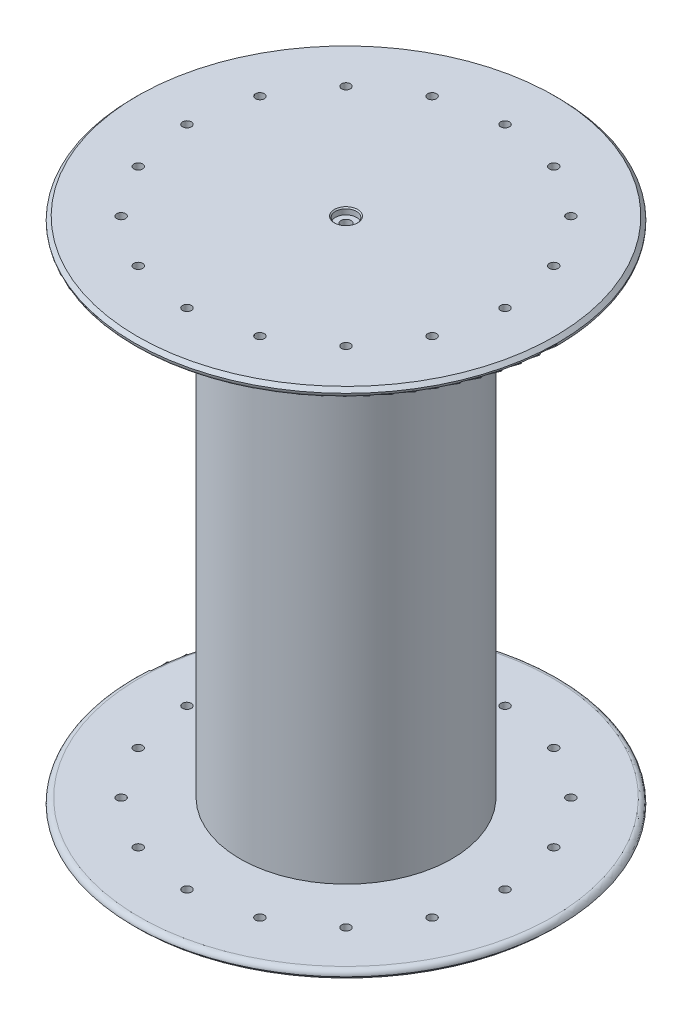
SolidWorks part; units mm, degrees
ref_plane "Front Plane" through (0, 0, 0) normal (0, 0, 1) x (1, 0, 0)
ref_plane "Top Plane" through (0, 0, 0) normal (0, 1, 0) x (1, 0, 0)
ref_plane "Right Plane" through (0, 0, 0) normal (1, 0, 0) x (0, 0, -1)
sketch "Sketch1" plane through (0, 0, 0) normal (0, 1, 0) x (1, 0, 0)
  circle A0 centre (0, 0) radius 60
  dimension "shaftdiameter" = 120
extrude "Boss-Extrude1" add sketch "Sketch1" along normal mid plane 280
ref_plane "Plane1" through (0, 50, 0) normal (0, 1, 0) x (1, 0, 0)
sketch "Sketch3" plane through (0, 140, 0) normal (0, 1, 0) x (1, 0, 0)
  circle A0 centre (0, 0) radius 120
  dimension "capdiameter" = 240
extrude "Boss-Extrude2" add sketch "Sketch3" along normal blind 5
chamfer "Chamfer1" distance 2 angle 45 1 edges at (0, 145, 120)
sketch "Sketch4" plane through (0, 145, 0) normal (0, 1, 0) x (1, 0, 0)
  line L0 (0, 120) -> (0, 60) construction
  line L1 (0, -60) -> (0, -120) construction
  line L2 (-92.1491, 76.867) -> (92.1491, -76.867) construction
  line L3 (-99.9988, -66.3343) -> (99.9988, 66.3343) construction
  circle A1 centre (0, 90) radius 2.5
  circle A2 centre (0, 0) radius 120 construction
  circle A3 centre (0, 0) radius 60 construction
  dimension "D1" = 5
fillet "Fillet1" radius 3 1 edges at (0, 140, 120)
hole_wizard "CBORE for #12 Binding Head Machine Screw2" positions "Sketch7" profile "Sketch8" counterbore size "#12" standard "ANSI Inch" end condition through all
sketch "Sketch7" plane through (0, 145, 0) normal (0, 1, 0) x (1, 0, 0)
  point P0 (0, 0)
sketch "Sketch8" plane through (0, 145, 0) normal (1, 0, 0) x (0, 0, 1)
  line L0 (0, 0) -> (0, 290)
  line L1 (0, 290) -> (2.8956, 290)
  line L3 (2.8956, 290) -> (2.8956, 3.5814)
  line L4 (5.9538, 3.5814) -> (2.8956, 3.5814)
  line L5 (5.9538, 3.5814) -> (5.9538, 0.635)
  line L6 (5.9538, 0.635) -> (6.5888, 0)
  line L7 (6.5888, 0) -> (0, 0)
  line L8 (-5.9538, 0.635) -> (-6.5888, 0) construction
  line L11 (0, -6.35) -> (0, 107.95) construction
  dimension "Thru Hole Dia." = 5.7912
  dimension "Thru Hole Depth" = 290
  dimension "C'Bore Dia." = 11.9075
  dimension "C'Bore Depth" = 3.5814
  dimension "Near C'Sink Dia." = 13.1775
  dimension "Near C'Sink Angle" = 90
mirror "Mirror8" about plane through (0, 0, 0) normal (0, 1, 0) of "Fillet1", "CBORE for #12 Binding Head Machine Screw2", "Chamfer1", "Boss-Extrude2"
extrude "Cut-Extrude1" cut sketch "Sketch4" against normal through all both and the other way through all
pattern_circular "CirPattern1" count 16 over 360 about axis through (0, 0, 0) along (0, 1, 0) of "Cut-Extrude1"
